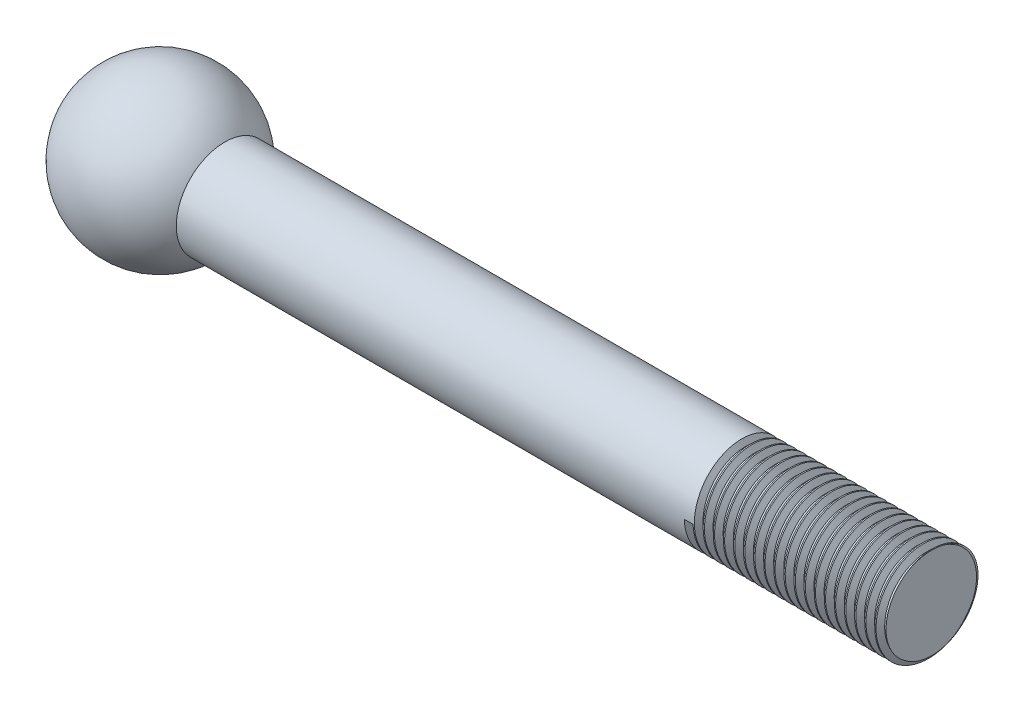
SolidWorks part; units mm, degrees
ref_plane "Front Plane" through (0, 0, 0) normal (0, 0, 1) x (1, 0, 0)
ref_plane "Top Plane" through (0, 0, 0) normal (0, 1, 0) x (1, 0, 0)
ref_plane "Right Plane" through (0, 0, 0) normal (1, 0, 0) x (0, 0, -1)
sketch "Sketch1" plane through (0, 0, 0) normal (0, 0, 1) x (1, 0, 0)
  line L0 (8, 6) -> (116, 6)
  line L1 (117, 5) -> (117, 0)
  line L2 (117, 0) -> (-10, 0)
  line L3 (0, 0) -> (-34.2629, 0) construction
  line L4 (116, 6) -> (117, 5)
  arc A0 (8, 6) -> (-10, 0) centre (0, 0) ccw
  point P4 (117, 6)
  point P10 (0, 0)
  dimension "D2" = 10
  dimension "D1" = 12
  dimension "D3" = 117
revolve "Revolve1" add sketch "Sketch1" angle 360 about L3
thread "Thread1" pitch 1.25 method cut profile "Thread Profile1" start angle 0, offset 0, length 45, pitch 1.25, diameter 12
ref_plane "Plane1" through (117, 0, 6) normal (0, -1, 0) x (0, 0, 1)
sketch "Thread Profile1" plane through (117, 0, 6) normal (0, -1, 0) x (0, 0, 1)
  line L0 (0, 0) -> (0, 1.25) construction
  line L11 (0, 0) -> (0, 1.0937)
  line L12 (0, 1.0937) -> (-0.6766, 0.7031)
  line L13 (-0.6766, 0.7031) -> (-0.6766, 0.3906)
  line L15 (-0.6766, 0.3906) -> (0, 0)
  line L17 (-0.6766, 0.5469) -> (0, 0.5469) construction
  point P2 (0, 0)
  dimension "Pitch" = 1.25
  dimension "Profile_Angle" = 60
  dimension "Profile_Land" = 0.3125
  dimension "Profile_Height" = 0.6766
sketch "Sketch4" plane through (0, 0, 0) normal (0, 1, 0) x (1, 0, 0)
  line L1 (121.7612, -22.7939) -> (95.5418, -22.7939)
  line L2 (121.7612, -22.7939) -> (121.7612, 22.7939)
  line L3 (121.7612, 22.7939) -> (95.5418, 22.7939)
  line L4 (95.5418, -22.7939) -> (95.5418, 22.7939)
  line L5 (121.7612, -22.7939) -> (95.5418, 22.7939) construction
  line L6 (121.7612, 22.7939) -> (95.5418, -22.7939) construction
  point P0 (108.6515, 0)
  dimension "D1" = 24
extrude "Cut-Extrude1" cut sketch "Sketch4" against normal blind 10 and the other way blind 10
